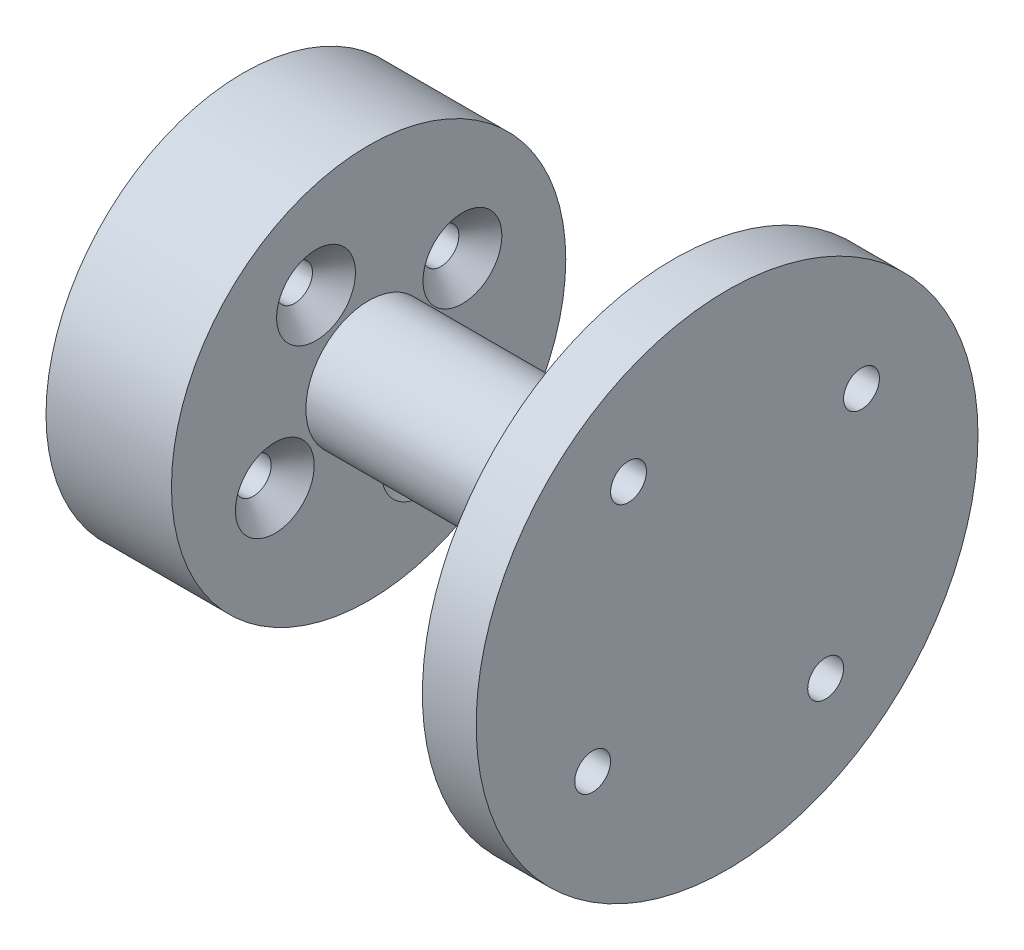
SolidWorks part; units mm, degrees
ref_plane "Спереди" through (0, 0, 0) normal (0, 0, 1) x (1, 0, 0)
ref_plane "Сверху" through (0, 0, 0) normal (0, 1, 0) x (1, 0, 0)
ref_plane "Справа" through (0, 0, 0) normal (1, 0, 0) x (0, 0, -1)
sketch "Эскиз1" plane through (0, 0, 0) normal (0, 0, 1) x (1, 0, 0)
  line L0 (0, 0) -> (100.9242, 0) construction
  line L6 (0, 10) -> (0, 11)
  line L7 (0, 11) -> (7, 11)
  line L11 (4, 10) -> (0, 10)
  line L13 (4, 10) -> (4, 0)
  line L14 (4, 0) -> (7, 0)
  line L15 (7, 0) -> (7, 11)
  dimension "D1" = 20
  dimension "D2" = 22
  dimension "D3" = 7
  dimension "D4" = 3
  dimension "D5" = 11
revolve "Повернуть1" add sketch "Эскиз1" angle 360 about L0 other way angle 360
hole_wizard "Зенковка для  винта с плоской головкой M22" positions "Эскиз4" profile "Эскиз5" countersink size "M2" standard "Ansi Metric" end condition through all
sketch "Эскиз4" plane through (7, 0, 0) normal (1, 0, 0) x (0, 0, -1)
  point P0 (-2.9334, 5.234)
  dimension "D1" = 6
sketch "Эскиз5" plane through (7, 5.234, 2.9334) normal (0, 1, 0) x (0, 0, -1)
  line L0 (0, 0) -> (0, 7)
  line L1 (0, 7) -> (1, 7)
  line L2 (1, 7) -> (1, 1.2)
  line L3 (1, 1.2) -> (2.2, 0)
  line L5 (2.2, 0) -> (0, 0)
  line L6 (-1, 1.2) -> (-2.2, 0) construction
  line L11 (0, -6.35) -> (0, 107.95) construction
  dimension "Диаметр сквозного отверстия" = 2
  dimension "Глубина сквозного отверстия" = 7
  dimension "Диаметр передней зенковки" = 4.4
  dimension "Угол передней зенковки" = 90
ref_axis "Ось1" through (4, 0, 0) along (-1, 0, 0)
ref_axis "Ось2" through (4, 0, 0) along (-1, 0, 0)
pattern_circular "Круговой массив2" count 4 over 360 about axis through (4, 0, 0) along (-1, 0, 0) of "Зенковка для  винта с плоской головкой M22"
sketch "Эскиз6" plane through (7, 0, 0) normal (1, 0, 0) x (0, 0, -1)
  circle A0 centre (0, 0) radius 3.5
  dimension "D1" = 7
extrude "Бобышка-Вытянуть1" add sketch "Эскиз6" along normal blind 17 contours A0
sketch "Эскиз7" plane through (24, 0, 0) normal (1, 0, 0) x (0, 0, -1)
  circle A0 centre (0, 0) radius 14
  dimension "D1" = 28
extrude "Бобышка-Вытянуть2" add sketch "Эскиз7" along normal blind 3 contours A0
sketch "Эскиз8" plane through (27, 0, 0) normal (1, 0, 0) x (0, 0, -1)
  circle A0 centre (-5.4991, 7.5) radius 1
  dimension "D1" = 2
  dimension "D2" = 9.3
  dimension "D3" = 7.5
extrude "Вырез-Вытянуть1" cut sketch "Эскиз8" against normal up to next contours A0
pattern_circular "Круговой массив3" count 4 over 360 about axis through (4, 0, 0) along (-1, 0, 0) of "Вырез-Вытянуть1"
